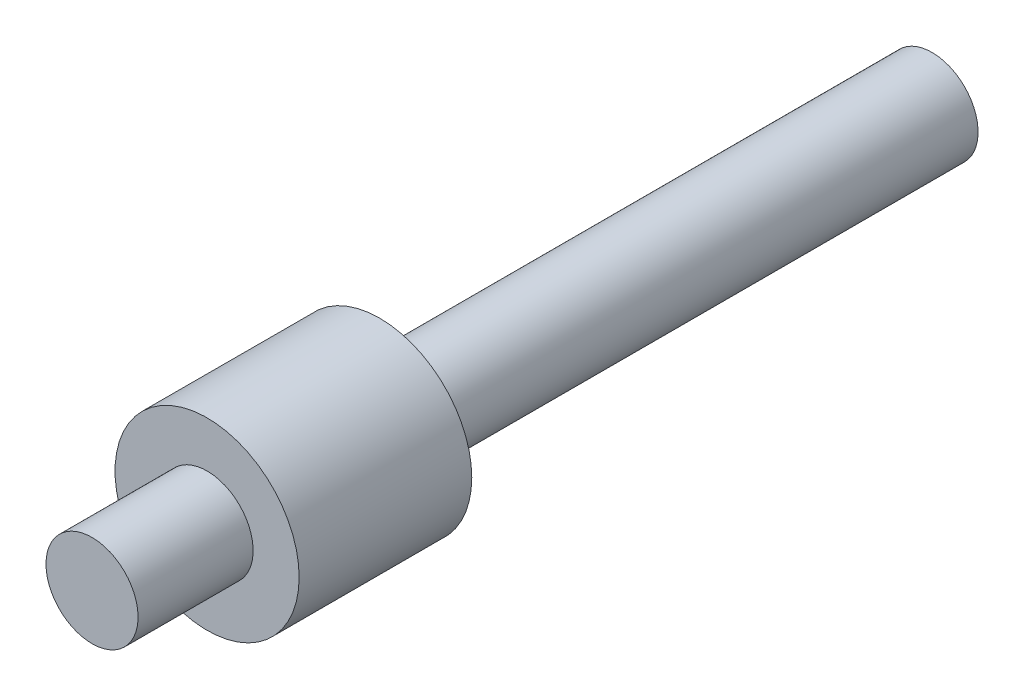
SolidWorks part; units mm, degrees
ref_plane "Front Plane" through (0, 0, 0) normal (0, 0, 1) x (1, 0, 0)
ref_plane "Top Plane" through (0, 0, 0) normal (0, 1, 0) x (1, 0, 0)
ref_plane "Right Plane" through (0, 0, 0) normal (1, 0, 0) x (0, 0, -1)
sketch "Sketch1" plane through (0, 0, 0) normal (0, 0, 1) x (1, 0, 0)
  circle A0 centre (0, 0) radius 2
  dimension "D1" = 4
extrude "Boss-Extrude1" add sketch "Sketch1" along normal blind 22.5
ref_plane "Plane1" through (0, 0, 10) normal (0, 0, -1) x (-1, 0, 0)
ref_plane "Plane2" through (0, 0, 17.5) normal (0, 0, 1) x (1, 0, 0)
sketch "Sketch3" plane through (0, 0, 17.5) normal (0, 0, 1) x (1, 0, 0)
  circle A0 centre (0, 0) radius 4
  dimension "D1" = 8
extrude "Boss-Extrude3" add sketch "Sketch3" against normal up to surface (7.5 mm away) up to plane "Plane1"
sketch "Sketch4" plane through (0, 0, 0) normal (0, 0, -1) x (-1, 0, 0)
  circle A0 centre (0, 0) radius 2
extrude "Boss-Extrude4" add sketch "Sketch4" along normal blind 14
